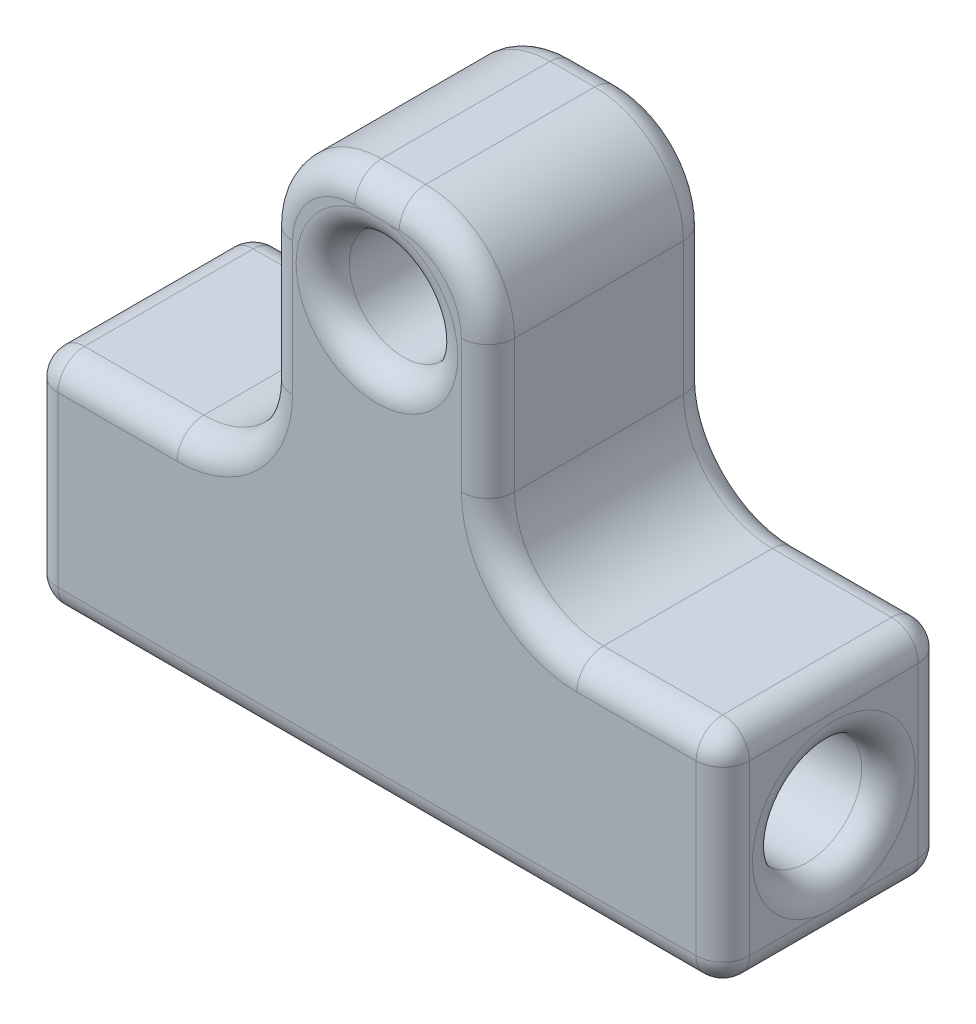
SolidWorks part; units mm, degrees
ref_plane "Front Plane" through (0, 0, 0) normal (0, 0, 1) x (1, 0, 0)
ref_plane "Top Plane" through (0, 0, 0) normal (0, 1, 0) x (1, 0, 0)
ref_plane "Right Plane" through (0, 0, 0) normal (1, 0, 0) x (0, 0, -1)
sketch "Sketch1" plane through (0, 0, 0) normal (0, 0, 1) x (1, 0, 0)
  line L0 (0, 42.6446) -> (0, -51.4876) construction
  line L1 (-40.9091, 0) -> (51.7355, 0) construction
  line L2 (22.5, -5) -> (38.9256, -5)
  line L3 (-2.5, 30) -> (2.5, 30)
  line L4 (-12.5, 20) -> (-12.5, 5)
  line L5 (-12.5, -30) -> (12.5, -30)
  line L6 (12.5, 20) -> (12.5, 5)
  line L7 (-12.5, 30) -> (12.5, -30) construction
  line L8 (-12.5, -30) -> (12.5, 30) construction
  line L9 (-38.9256, -5) -> (-22.5, -5)
  line L10 (-38.9256, -5) -> (-38.9256, -30)
  line L11 (-38.9256, -30) -> (38.9256, -30)
  line L12 (38.9256, -5) -> (38.9256, -30)
  line L13 (-38.9256, -5) -> (38.9256, -30) construction
  line L14 (-38.9256, -30) -> (38.9256, -5) construction
  arc A0 (2.5, 30) -> (12.5, 20) centre (2.5, 20) cw
  arc A1 (-2.5, 30) -> (-12.5, 20) centre (-2.5, 20) ccw
  arc A2 (12.5, 5) -> (22.5, -5) centre (22.5, 5) ccw
  arc A3 (-12.5, 5) -> (-22.5, -5) centre (-22.5, 5) cw
  circle A4 centre (0, 18) radius 6.1
  point P5 (0, 0)
  point P10 (0, -17.5)
  point P25 (12.5, -5)
  dimension "D4" = 10
  dimension "D5" = 12.2
  dimension "D1" = 25
  dimension "D2" = 60
  dimension "D3" = 25
  dimension "D6" = 12
extrude "Boss-Extrude1" add sketch "Sketch1" along normal blind 25 contours A3 L9 L10 L11 L12 L2 A2 L6 A0 L3 A1 L4 | A4
sketch "Sketch2" plane through (38.9256, 0, 0) normal (1, 0, 0) x (0, 0, -1)
  line L0 (-12.5, -5) -> (-12.5, -30) construction
  line L1 (-25, -5) -> (0, -5) construction
  line L2 (-25, -30) -> (0, -30) construction
  circle A0 centre (-12.5, -18) radius 6.15
  dimension "D1" = 12.3
  dimension "D2" = 12
extrude "Cut-Extrude1" cut sketch "Sketch2" against normal through all
fillet "Fillet1" radius 3 32 edges at (-38.9256, -5, 12.5) (-38.9256, -30, 12.5) (-38.9256, -18, 6.35) (6.1, 18, 0) (-15.4289, -2.0711, 0) (-30.7128, -5, 0) (-38.9256, -17.5, 0) (0, -30, 0) (15.4289, -2.0711, 0) (12.5, 12.5, 0) (9.5711, 27.0711, 0) (0, 30, 0) (-9.5711, 27.0711, 0) (-12.5, 12.5, 0) (30.7128, -5, 0) (6.1, 18, 25) (-9.5711, 27.0711, 25) (0, 30, 25) (9.5711, 27.0711, 25) (12.5, 12.5, 25) (15.4289, -2.0711, 25) (30.7128, -5, 25) (0, -30, 25) (-38.9256, -17.5, 25) (-30.7128, -5, 25) (-15.4289, -2.0711, 25) (-12.5, 12.5, 25) (38.9256, -30, 12.5) (38.9256, -17.5, 25) (38.9256, -5, 12.5) (38.9256, -17.5, 0) (38.9256, -18, 6.35)
